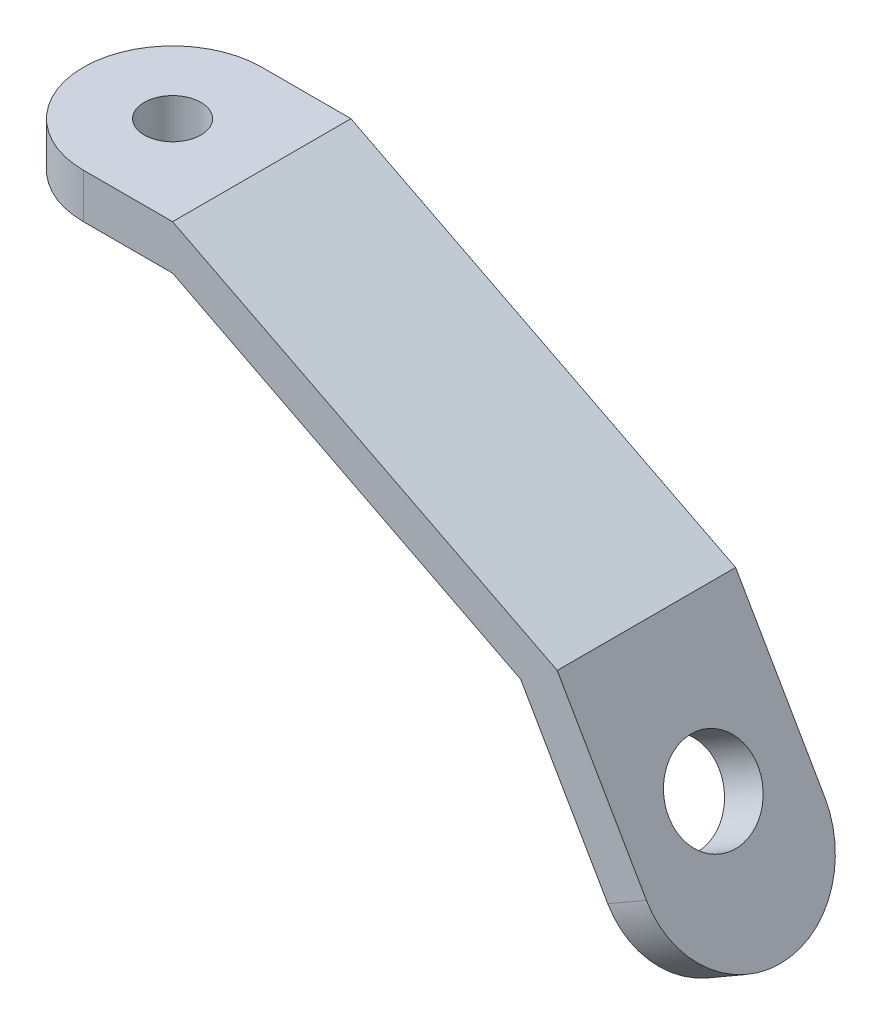
SolidWorks part; units mm, degrees
ref_plane "Front Plane" through (0, 0, 0) normal (0, 0, 1) x (1, 0, 0)
ref_plane "Top Plane" through (0, 0, 0) normal (0, 1, 0) x (1, 0, 0)
ref_plane "Right Plane" through (0, 0, 0) normal (1, 0, 0) x (0, 0, -1)
sketch "Sketch1" plane through (0, 0, 0) normal (0, 0, 1) x (1, 0, 0)
  line L0 (0, 0) -> (0, 138.9357) construction
  line L1 (0, 0) -> (124.731, 72.0135) construction
  line L2 (-10, 70) -> (10, 70)
  line L3 (10, 70) -> (53.1218, 47.9904)
  line L4 (53.1218, 47.9904) -> (68.1218, 22.0096)
  line L5 (-10, 70) -> (-10, 65)
  line L6 (-10, 65) -> (10, 65)
  line L7 (10, 65) -> (49.0289, 45.0794)
  line L8 (49.0289, 45.0794) -> (63.7917, 19.5096)
  line L9 (63.7917, 19.5096) -> (68.1218, 22.0096)
  arc A0 (60.6218, 35) -> (0, 70) centre (0, 0) ccw construction
  dimension "D1" = 60
  dimension "D4" = 70
  dimension "D2" = 30
  dimension "D3" = 20
  dimension "D5" = 5
extrude "Boss-Extrude1" add sketch "Sketch1" along normal mid plane 20
sketch "Sketch2" plane through (0, 70, 0) normal (0, 1, 0) x (1, 0, 0)
  circle A0 centre (0, 0) radius 3.175
  dimension "D1" = 6.35
extrude "Cut-Extrude1" cut sketch "Sketch2" against normal through all
sketch "Sketch3" plane through (60.6218, 35, 0) normal (0.866, 0.5, 0) x (0, 0, -1)
  circle A0 centre (0, 0) radius 5
  dimension "D1" = 10
extrude "Cut-Extrude2" cut sketch "Sketch3" against normal through all
fillet "Fillet1" radius 10 4 edges at (65.9567, 20.7596, -10) (65.9567, 20.7596, 10) (-10, 67.5, -10) (-10, 67.5, 10)
